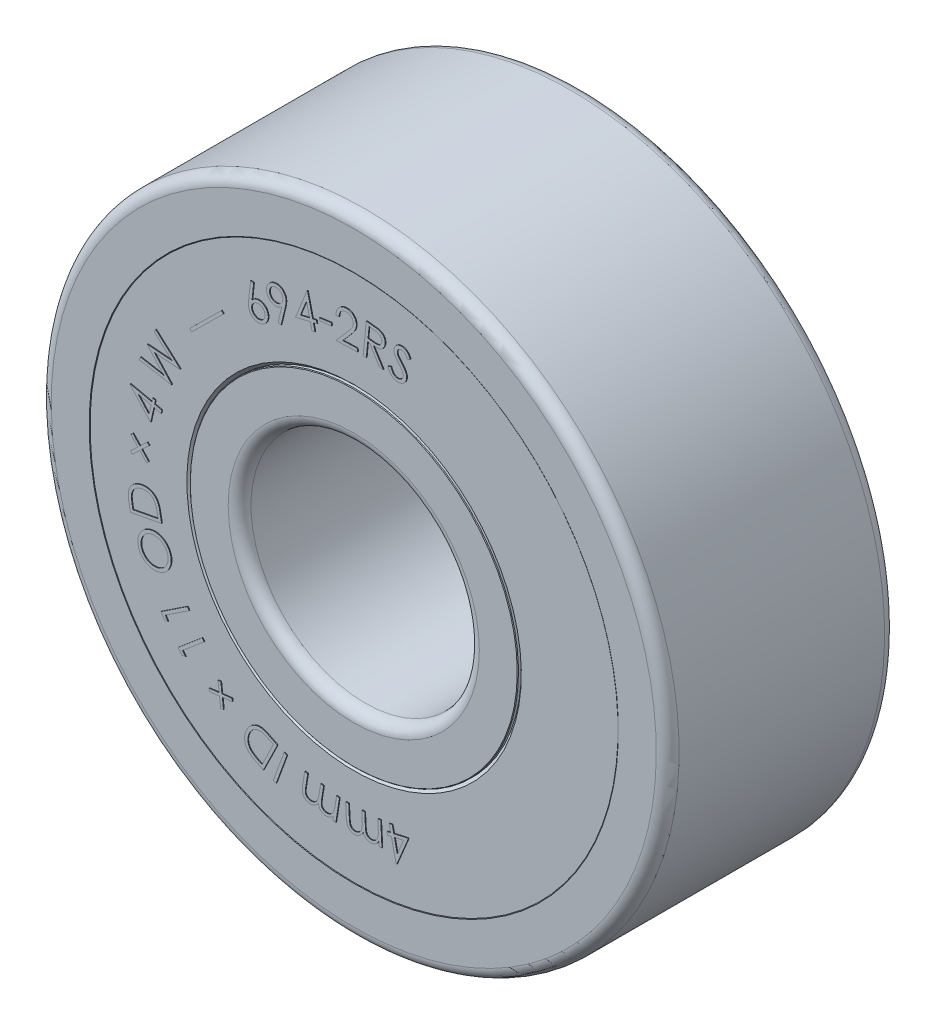
SolidWorks part; units mm, degrees
material "AISI 316 Annealed Stainless Steel Bar (SS)"
ref_plane "Front" through (0, 0, 0) normal (0, 0, 1) x (1, 0, 0)
ref_plane "Top" through (0, 0, 0) normal (0, 1, 0) x (1, 0, 0)
ref_plane "Right" through (0, 0, 0) normal (1, 0, 0) x (0, 0, -1)
sketch "LAYOUT R" plane through (0, 0, 0) normal (1, 0, 0) x (0, 0, -1)
  line L0 (-2, 2) -> (2, 2)
  line L1 (2, -5.5) -> (-2, -5.5) construction
  line L2 (2, -5.5) -> (2, 5.5) construction
  line L3 (2, 5.5) -> (-2, 5.5)
  line L4 (-2, -5.5) -> (-2, 5.5) construction
  line L5 (2, -5.5) -> (-2, 5.5) construction
  line L6 (2, 5.5) -> (-2, -5.5) construction
  line L7 (-2, 2.875) -> (2, 2.875)
  line L8 (-2, 4.625) -> (2, 4.625)
  line L11 (-3.81, 0) -> (3.81, 0) construction
  line L12 (-2, 5.5) -> (-2, 4.625)
  line L13 (2, 5.5) -> (2, 4.625)
  line L14 (-2, 4.625) -> (-2, 2.875)
  line L15 (2, 4.625) -> (2, 2.875)
  line L16 (-2, 2.875) -> (-2, 2)
  line L17 (2, 2.875) -> (2, 2)
  line L18 (-1.9945, 4.625) -> (-1.9945, 2.875)
  line L19 (1.9945, 4.625) -> (1.9945, 2.875)
  point P0 (0, 0)
  point P15 (0, 0)
  dimension "D1" = 4
  dimension "D2" = 11
  dimension "D3" = 2
  dimension "D6" = 0.0055
  dimension "D7" = 0.0055
  dimension "D4" = 2.875
  dimension "D5" = 4.625
sketch "Sketch R, INNER BODY" plane through (0, 0, 0) normal (1, 0, 0) x (0, 0, -1)
  line L0 (-2, 2) -> (2, 2) construction
  line L2 (-2, 2.875) -> (2, 2.875) construction
  line L4 (-2, 2) -> (2, 2)
  line L6 (-2, 2.875) -> (2, 2.875)
  line L8 (2, 2.875) -> (2, 2) construction
  line L9 (-2, 2.875) -> (-2, 2) construction
  line L10 (2, 2.875) -> (2, 2)
  line L11 (-2, 2.875) -> (-2, 2)
  line L12 (-3.81, 0) -> (3.81, 0) construction
  line L13 (-3.81, 0) -> (3.81, 0) construction
sketch "Sketch R, OUTER BODY" plane through (0, 0, 0) normal (1, 0, 0) x (0, 0, -1)
  line L0 (-2, 4.625) -> (2, 4.625) construction
  line L1 (2, 5.5) -> (2, 4.625) construction
  line L8 (-3.81, 0) -> (3.81, 0) construction
  line L9 (-3.81, 0) -> (3.81, 0) construction
  line L16 (2, 5.5) -> (-2, 5.5) construction
  line L17 (-2, 5.5) -> (-2, 4.625) construction
  line L18 (-2, 4.625) -> (2, 4.625)
  line L19 (2, 5.5) -> (2, 4.625)
  line L22 (2, 5.5) -> (-2, 5.5)
  line L23 (-2, 5.5) -> (-2, 4.625)
sketch "Sketch R, SEAL FACES" plane through (0, 0, 0) normal (1, 0, 0) x (0, 0, -1)
  line L0 (-3.81, 0) -> (3.81, 0) construction
  line L1 (-3.81, 0) -> (3.81, 0) construction
  line L3 (-2, 2.875) -> (2, 2.875) construction
  line L5 (-2, 4.625) -> (2, 4.625) construction
  line L7 (-1.9945, 2.875) -> (1.9945, 2.875)
  line L9 (-1.9945, 4.625) -> (1.9945, 4.625)
  line L10 (1.9945, 4.625) -> (1.9945, 2.875) construction
  line L11 (-1.9945, 4.625) -> (-1.9945, 2.875) construction
  line L12 (1.9945, 4.625) -> (1.9945, 2.875)
  line L13 (-1.9945, 4.625) -> (-1.9945, 2.875)
revolve "Revolve INNER BODY" add sketch "Sketch R, INNER BODY" angle 360 about L13
fillet "Fillet INNER BODY" radius 0.2 2 edges at (0, -2, 2) (0, -2, -2)
chamfer "Chamfer INNER BODY" distance 0.011 angle 45 2 edges at (0, -2.875, -2) (0, -2.875, 2)
revolve "Revolve OUTER BODY" add sketch "Sketch R, OUTER BODY" angle 360 about L9
fillet "Fillet OUTER BODY" radius 0.2 2 edges at (0, -5.5, 2) (0, -5.5, -2)
chamfer "Chamfer OUTER BODY" distance 0.011 angle 45 2 edges at (0, -4.625, 2) (0, -4.625, -2)
revolve "Revolve SEALS" add sketch "Sketch R, SEAL FACES" angle 360 about L1
chamfer "Chamfer SEALS" distance 0.055 angle 45 2 edges at (0, -2.875, -1.9945) (0, -2.875, 1.9945)
sketch "Sketch TEXT RADIUS 1 — MANUALLY ASSIGN TEXT AND FONT SIZE (FROM EQUATIONS)" plane through (0, 0, 1.9945) normal (0, 0, 1) x (1, 0, 0)
  circle A0 centre (0, 0) radius 3.47 construction
  text T0 "4mm ID × 11 OD × 4 W  —  694-2RS" font "Century Gothic" height 0.56
  dimension "D1" = 6.94
extrude "Boss-Extrude SEAL LABEL 1" add sketch "Sketch TEXT RADIUS 1 — MANUALLY ASSIGN TEXT AND FONT SIZE (FROM EQUATIONS)" along normal blind 0.013
sketch "Sketch TEXT RADIUS 2 — MANUALLY ASSIGN TEXT AND FONT SIZE (FROM EQUATIONS)" plane through (0, 0, -1.9945) normal (0, 0, -1) x (-1, 0, 0)
  circle A0 centre (0, 0) radius 3.47 construction
  text T0 "4mm ID × 11 OD × 4 W  —  694-2RS" font "Century Gothic" height 0.56
  dimension "D1" = 6.94
extrude "Boss-Extrude SEAL LABEL 2" add sketch "Sketch TEXT RADIUS 2 — MANUALLY ASSIGN TEXT AND FONT SIZE (FROM EQUATIONS)" along normal blind 0.013
equation "\"_i__BORE\" = 4"
equation "\"_i__OUTSIDE_DIAMETER\" = 11"
equation "\"_i__WIDTH\"= 4"
equation "\"_user_applied_FONT_SIZE\"= int ( \"BODY_SPAN__SEAL__OF_RADIUS\" * \"g_param__FONT_SIZE_RATIO\" * 100 ) / 100'MANUALLY ASSIGN TO FONT"
equation "\"BODY__HALF_WIDTH\"= \"_i__WIDTH\" / 2"
equation "\"BODY_SPAN___OF_DIAMETER\"= \"_i__OUTSIDE_DIAMETER\" - \"_i__BORE\""
equation "\"BODY_SPAN___OF_RADIUS\"= \"BODY_SPAN___OF_DIAMETER\" / 2"
equation "\"BODY_SPAN__BORE_AND_OD__OF RADIUS\"= ( \"BODY_SPAN___OF_RADIUS\" - \"BODY_SPAN__SEAL__OF_RADIUS\" ) / 2"
equation "\"BODY_SPAN__SEAL__OF_RADIUS\"= \"BODY_SPAN___OF_RADIUS\" * \"g_param__SEAL_PANEL_SPAN__RATIO_OF_BODY_RADIAN\""
equation "\"BORE__RADIUS\"= \"_i__BORE\" / 2"
equation "\"CORNER_RADII\"= \"_i__WIDTH\" * \"g_param__CORNER_RADII__RATIO_TO_WIDTH\""
equation "\"RING_INNER__OUTSIDE_RADIUS\"= \"BORE__RADIUS\" + \"BODY_SPAN__BORE_AND_OD__OF RADIUS\""
equation "\"RING_OUTER__OUTSIDE_RADIUS\"= ( \"_i__OUTSIDE_DIAMETER\" / 2 ) - \"BODY_SPAN__BORE_AND_OD__OF RADIUS\""
equation "\"SEAL_CHAMFERS\"= \"_i__OUTSIDE_DIAMETER\" * \"g_param__SEAL_CHAMFERS__RATIO_TO_OD\""
equation "\"SEAL_FACE_INSET\"= \"SIDE_FACE_CHAMFERS\""
equation "\"SIDE_FACE_CHAMFERS\"= \"_i__OUTSIDE_DIAMETER\" * \"g_param__SIDE_CHAMFERS__RATIO_TO_OD\""
equation "\"TEXT_RADIUS\"= \"_i__BORE\" + ( \"BODY_SPAN___OF_DIAMETER\" / 2 ) - \"_user_applied_FONT_SIZE\""
equation "\"D1@Boss-Extrude SEAL LABEL 1\" = \"g_param__INDICIA__EXTRUSION_HEIGHT\""
equation "\"D1@Boss-Extrude SEAL LABEL 2\" = \"g_param__INDICIA__EXTRUSION_HEIGHT\""
equation "\"D1@Chamfer INNER BODY\"=\"SIDE_FACE_CHAMFERS\""
equation "\"D1@Chamfer OUTER BODY\"=\"SIDE_FACE_CHAMFERS\""
equation "\"D1@Chamfer SEALS\"=\"SEAL_CHAMFERS\""
equation "\"D1@Fillet INNER BODY\"=\"CORNER_RADII\""
equation "\"D1@Fillet OUTER BODY\"=\"CORNER_RADII\""
equation "\"D1@LAYOUT R\"=\"_i__WIDTH\""
equation "\"D1@Sketch TEXT RADIUS 1 — MANUALLY ASSIGN TEXT AND FONT SIZE (FROM EQUATIONS)\" = \"TEXT_RADIUS\""
equation "\"D1@Sketch TEXT RADIUS 2 — MANUALLY ASSIGN TEXT AND FONT SIZE (FROM EQUATIONS)\" = \"TEXT_RADIUS\""
equation "\"D2@LAYOUT R\"=\"_i__OUTSIDE_DIAMETER\""
equation "\"D3@LAYOUT R\"=\"BORE__RADIUS\""
equation "\"D4@LAYOUT R\"=\"RING_INNER__OUTSIDE_RADIUS\""
equation "\"D5@LAYOUT R\"=\"RING_OUTER__OUTSIDE_RADIUS\""
equation "\"g_param__CORNER_RADII__RATIO_TO_WIDTH\"= 0.05'ISO MAX IS 0.07 WHERE WIDTH IS LESS THAN DIAMETER"
equation "\"g_param__FONT_SIZE_RATIO\"= 0.32'EXPRESSES RADIAL PROPORTION OF SEAL FACE"
equation "\"g_param__INDICIA__EXTRUSION_HEIGHT\"=0.013'RAISED INDICIA ON SEAL FACES"
equation "\"g_param__SEAL_CHAMFERS__RATIO_TO_OD\"= 0.005"
equation "\"g_param__SEAL_PANEL_SPAN__RATIO_OF_BODY_RADIAN\"= 0.5'ISO-UNSPECIFIED"
equation "\"g_param__SIDE_CHAMFERS__RATIO_TO_OD\"= 0.001'NOT ISO-SPECIFIED"
